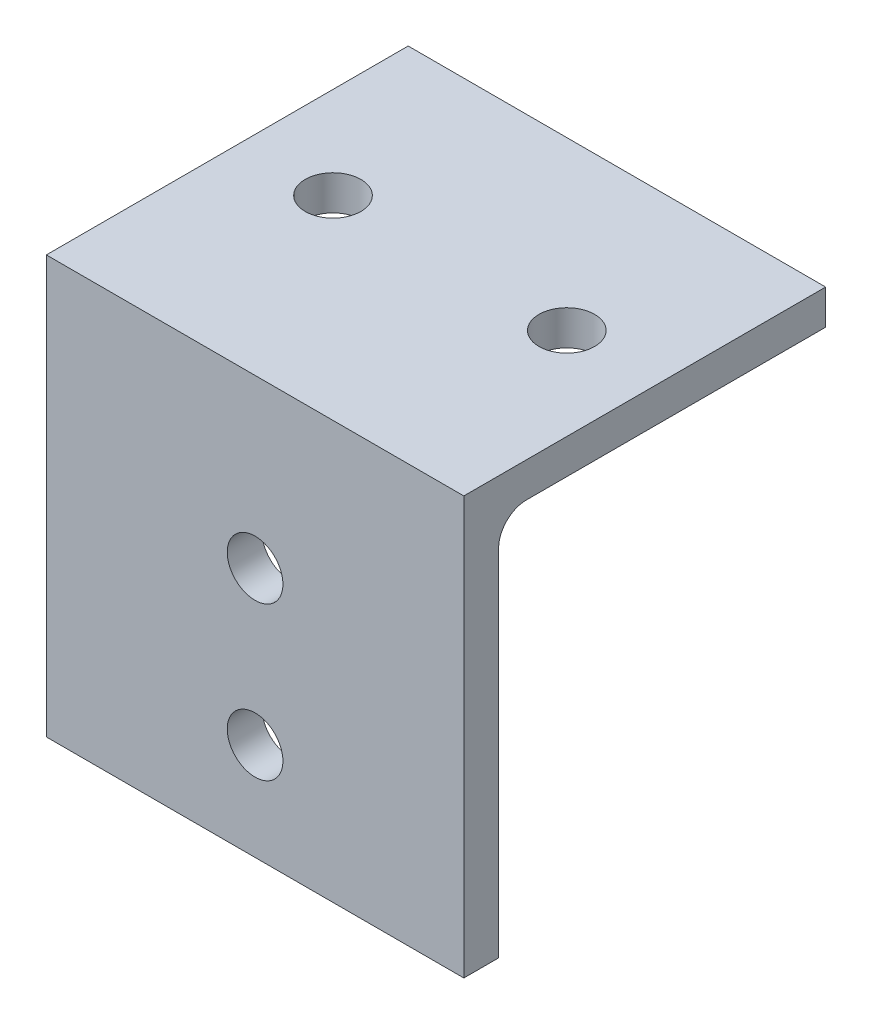
SolidWorks part; units mm, degrees
ref_plane "Front Plane" through (0, 0, 0) normal (0, 0, 1) x (1, 0, 0)
ref_plane "Top Plane" through (0, 0, 0) normal (0, 1, 0) x (1, 0, 0)
ref_plane "Right Plane" through (0, 0, 0) normal (1, 0, 0) x (0, 0, -1)
sketch "Sketch1" plane through (0, 0, 0) normal (0, 1, 0) x (1, 0, 0)
  line L0 (-19.5834, -8.6292) -> (18.5166, -8.6292) construction
  line L1 (-19.5834, 16.7708) -> (-5.08, 16.7708)
  line L2 (-19.5834, 16.7708) -> (-19.5834, -13.0742)
  line L3 (-19.5834, -13.0742) -> (18.5166, -13.0742)
  line L4 (18.5166, 16.7708) -> (18.5166, -13.0742)
  line L5 (-19.5834, 1.5308) -> (18.5166, 1.5308) construction
  line L6 (-5.08, 16.7708) -> (5.08, 16.7708)
  line L12 (5.08, 16.7708) -> (18.5166, 16.7708)
  circle A1 centre (-11.2014, 1.5308) radius 2.54
  circle A2 centre (10.1346, 1.5308) radius 2.54
  dimension "D1" = 25.4
  dimension "D4" = 5.08
  dimension "D5" = 5.08
  dimension "D2" = 38.1
  dimension "D3" = 29.845
  dimension "D6" = 8.382
  dimension "D7" = 8.382
  dimension "D8" = 15.24
extrude "Boss-Extrude1" add sketch "Sketch1" along normal blind 3.175
sketch "Sketch2" plane through (0, 0, 13.0742) normal (0, 0, 1) x (1, 0, 0)
  line L0 (18.5166, 3.175) -> (18.5166, 0) construction
  line L1 (-19.5834, 3.175) -> (18.5166, 3.175)
  line L2 (-19.5834, 3.175) -> (-19.5834, -34.925)
  line L3 (-19.5834, -34.925) -> (18.5166, -34.925)
  line L4 (18.5166, 3.175) -> (18.5166, -34.925)
  line L5 (-0.5334, 3.175) -> (-0.5334, -34.925) construction
  circle A0 centre (-0.5334, -12.065) radius 2.54
  circle A1 centre (-0.5334, -26.035) radius 2.54
  dimension "D2" = 5.08
  dimension "D3" = 5.08
  dimension "D1" = 38.1
  dimension "D4" = 13.97
  dimension "D5" = 15.24
extrude "Boss-Extrude2" add sketch "Sketch2" along normal blind 3.175
fillet "Fillet2" radius 2.54 1 edges at (-0.5334, 0, 13.0742)
